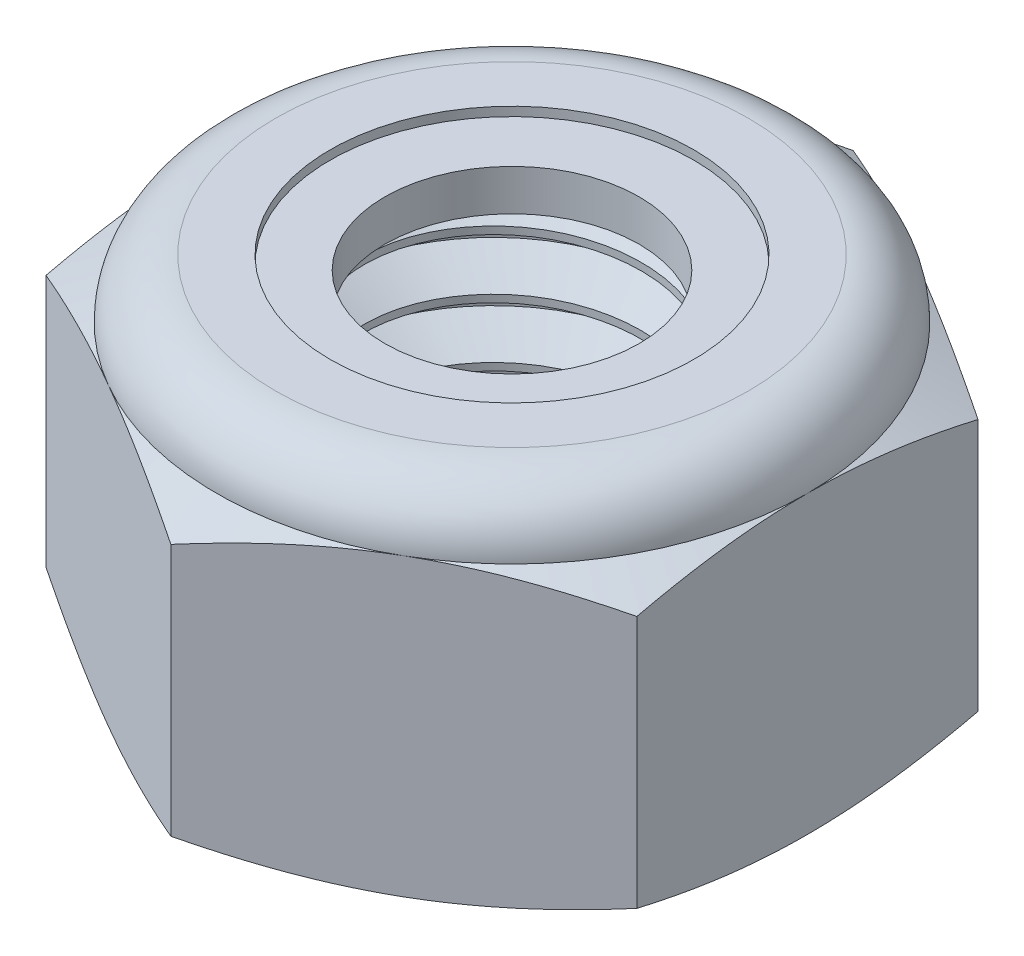
SolidWorks part; units mm, degrees
ref_plane "Front" through (0, 0, 0) normal (0, 0, 1) x (1, 0, 0)
ref_plane "Top" through (0, 0, 0) normal (0, 1, 0) x (1, 0, 0)
ref_plane "Right" through (0, 0, 0) normal (1, 0, 0) x (0, 0, -1)
sketch "Sketch1" plane through (0, 0, 0) normal (0, 1, 0) x (1, 0, 0)
  line L0 (0, 0) -> (2.1213, -2.1213) construction
  line L1 (0, 5.7735) -> (-5, 2.8868)
  line L2 (-5, 2.8868) -> (-5, -2.8868)
  line L3 (-5, -2.8868) -> (0, -5.7735)
  line L4 (0, -5.7735) -> (5, -2.8868)
  line L5 (5, -2.8868) -> (5, 2.8868)
  line L6 (5, 2.8868) -> (0, 5.7735)
  circle A0 centre (0, 0) radius 5 construction
  circle A1 centre (0, 0) radius 3
  point P12 (2.1213, -2.1213)
  dimension "Thread Dia" = 6
  dimension "Hex Flats" = 10
  dimension "D1" = 45
extrude "Extrude1" add sketch "Sketch1" along normal blind 6
chamfer "Chamfer1" distance 0.3 angle 45 1 edges at (0, 0, 3)
sketch "Sketch5" plane through (0, 0, 0) normal (1, 0, 0) x (0, 0, -1)
  line L0 (0, 0) -> (5, 0)
  line L1 (5, 0) -> (5.7735, 0.3607)
  line L2 (5.7735, 0.3607) -> (5.7735, 4.6393)
  line L3 (5.7735, 4.6393) -> (5, 5)
  line L4 (4, 6) -> (4, 7.27)
  line L5 (4, 7.27) -> (7.0435, 7.27)
  line L6 (7.0435, 7.27) -> (7.0435, -1.27)
  line L7 (7.0435, -1.27) -> (0, -1.27)
  line L8 (0, -1.27) -> (0, 0)
  line L9 (5, 5) -> (5, 0) construction
  line L10 (2.8868, 6) -> (5.7735, 6) construction
  line L13 (5.7735, 2.5) -> (7.0435, 2.5) construction
  line L14 (5.7735, 6) -> (5.7735, 0) construction
  line L15 (0, 0) -> (0, 7.27) construction
  line L20 (0, 7.27) -> (4, 7.27) construction
  arc A0 (5, 5) -> (4, 6) centre (4, 5) ccw
  dimension "D1" = 25
  dimension "D2" = 1.27
  dimension "D4" = 1
revolve "Cut-Revolve3" cut sketch "Sketch5" angle 360 about L15
sketch "Sketch6" plane through (0, 0, 0) normal (1, 0, 0) x (0, 0, -1)
  line L0 (0, 5) -> (4.8476, 5)
  line L1 (4, 5.8476) -> (3.0762, 5.8476)
  line L2 (0, 7.27) -> (0, 5)
  line L3 (3.0762, 7.27) -> (0, 7.27)
  line L4 (0, 7.27) -> (4, 7.27) construction
  line L5 (0, 0) -> (0, 7.27) construction
  line L6 (0, 7.27) -> (0, 0) construction
  line L7 (3.0762, 5.8476) -> (3.0762, 7.27)
  line L8 (4, 6) -> (4, 5.8476) construction
  line L9 (3.0762, 5.8476) -> (2.9238, 5.8476) construction
  line L21 (3, 5.8476) -> (3, 6) construction
  arc A0 (4.8476, 5) -> (4, 5.8476) centre (4, 5) ccw
  arc A1 (5, 5) -> (4, 6) centre (4, 5) ccw construction
  dimension "D1" = 0.1524
revolve "Cut-Revolve4" cut sketch "Sketch6" angle 360 about L6
sketch "Sketch7" plane through (0, 0, 0) normal (1, 0, 0) x (0, 0, -1)
  line L0 (2.1524, 5.0762) -> (4.7676, 5.0762)
  line L1 (4, 5.7714) -> (2.1524, 5.7714)
  line L2 (2.1524, 5.7714) -> (2.1524, 5.0762)
  line L3 (2.1524, 5.0762) -> (0, 5.0762) construction
  line L4 (0, 5.0762) -> (0, 5.7714) construction
  line L5 (0, 5.7714) -> (2.1524, 5.7714) construction
  line L6 (2.1524, 5.0762) -> (2.1524, 5) construction
  line L7 (0, 5) -> (4.8476, 5) construction
  line L8 (4, 5.7714) -> (4, 5.8476) construction
  line L10 (2.1524, 5.8476) -> (3.0762, 5.8476) construction
  line L11 (4, 5.8476) -> (3.0762, 5.8476) construction
  arc A0 (4.7676, 5.0762) -> (4, 5.7714) centre (4, 5) ccw
  arc A2 (4.8476, 5) -> (4, 5.8476) centre (4, 5) ccw construction
  dimension "D1" = 0.0762
revolve "Revolve2" add sketch "Sketch7" angle 360 about L4
ref_axis "Center Axis 1" through (0, 5, 0) along (0, -1, 0)
sketch "Sketch12" plane through (0, 0, 0) normal (0, -1, 0) x (1, 0, 0)
  circle A0 centre (0, 0) radius 3
  circle A1 centre (0, 0) radius 3 construction
extrude "Boss-Extrude3" add sketch "Sketch12" against normal up to vertex (5 mm away) up to point (0, 5, -4.8476)
sketch "Sketch2" plane through (0, 0, 0) normal (1, 0, 0) x (0, 0, -1)
  line L1 (0, 0) -> (3, 0)
  line L2 (0, 0) -> (0, 5.8476)
  line L3 (0, 5.8476) -> (3, 5.8476)
  line L4 (3, 0) -> (3, 5.8476)
  line L7 (0, -3) -> (0, 0) construction
  line L11 (4, 5.8476) -> (3.0762, 5.8476) construction
revolve "Revolve1" add sketch "Sketch2" angle 360 about L7
sketch "Sketch8" plane through (0, 0, 0) normal (0, -1, 0) x (1, 0, 0)
  circle A0 centre (0, 0) radius 3 construction
  circle A2 centre (0, 0) radius 3
curve "Helix/Spiral1" pitch 1 height 12 radius 3 centre (0, 0, 0) axis (0, 1, 0) start towards (0, 0, -1) parameters "Pitch"=1
sketch "Sketch9" plane through (0, 0, 0) normal (1, 0, 0) x (0, 0, -1)
  line L0 (3, -0.875) -> (3, 0)
  line L1 (3, -0.875) -> (2.3505, -0.5)
  line L2 (2.3505, -0.5) -> (2.3505, -0.375)
  line L3 (2.3505, -0.375) -> (3, 0)
  line L4 (-3, 0) -> (3, 0) construction
  line L5 (3, -0.4375) -> (2.3505, -0.4375) construction
  line L6 (2.6752, -0.6875) -> (2.6752, -0.1875) construction
  dimension "D1" = 0.125
  dimension "D2" = 0.5
  dimension "D3" = 60
sweep "Cut-Sweep1" cut profiles "Sketch9" path "Helix/Spiral1" align with end faces yes
combine bodies "Combine1" operation type subtract main body 135 bodies to subtract 132
sketch "Sketch14" plane through (0, 0, 0) normal (1, 0, 0) x (0, 0, -1)
  line L0 (0, 0) -> (0, 6) construction
  line L1 (3.0762, 6) -> (-3.0762, 6) construction
  line L2 (-3.3, 0) -> (-1.5, 1.8)
  line L4 (-3, 0) -> (-3.3, 0)
  line L9 (-1.5, 1.8) -> (0, 1.8)
  line L10 (0, 1.8) -> (0, 0)
  line L11 (0, 0) -> (-3, 0)
  line L12 (-1.5, 1.8) -> (-1.5, 0) construction
  dimension "D1" = 45
  dimension "D2" = 6
  dimension "D3" = 0.3
revolve "Cut-Revolve5" cut sketch "Sketch14" angle 360 about L0
equation "\"D4@Sketch5\"=\"Height@Extrude1\"/6"
equation "\"D3@Helix/Spiral1\"=2*\"Height@Extrude1\""
equation "\"D1@Sketch9\"=\"Pitch@Helix/Spiral1\"*.125"
equation "\"D2@Sketch9\"=\"Pitch@Helix/Spiral1\"*.50"
equation "\"D1@Chamfer1\"=.05*\"Thread Dia@Sketch1\""
equation "\"D2@Sketch14\"=\"Thread Dia@Sketch1\""
equation "\"D3@Sketch14\"=\"D1@Chamfer1\""
